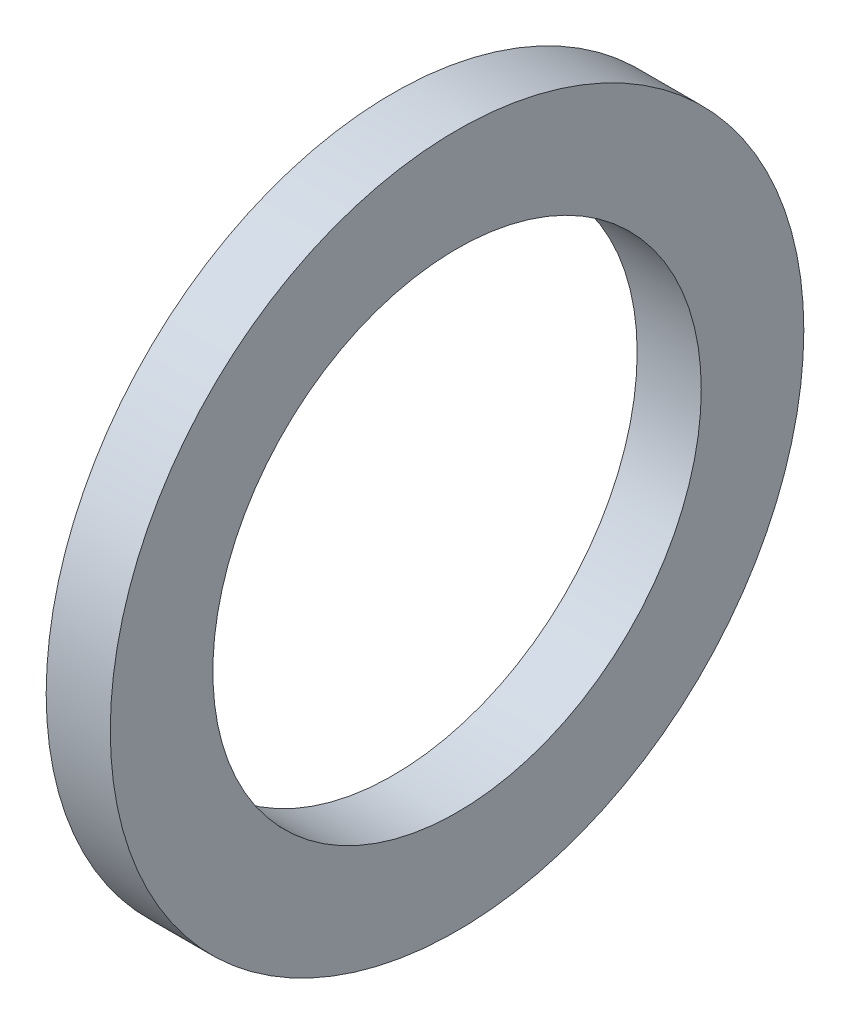
SolidWorks part; units mm, degrees
ref_plane "Front Plane" through (0, 0, 0) normal (0, 0, 1) x (1, 0, 0)
ref_plane "Top Plane" through (0, 0, 0) normal (0, 1, 0) x (1, 0, 0)
ref_plane "Right Plane" through (0, 0, 0) normal (1, 0, 0) x (0, 0, -1)
sketch "Sketch1" plane through (0, 0, 0) normal (1, 0, 0) x (0, 0, -1)
  circle A0 centre (0, 0) radius 3.81
  circle A1 centre (0, 0) radius 5.41
  dimension "D1" = 7.62
  dimension "D2" = 1.6
extrude "Boss-Extrude1" add sketch "Sketch1" along normal blind 1
equation "\"D1@Boss-Extrude1\"=1mm"
